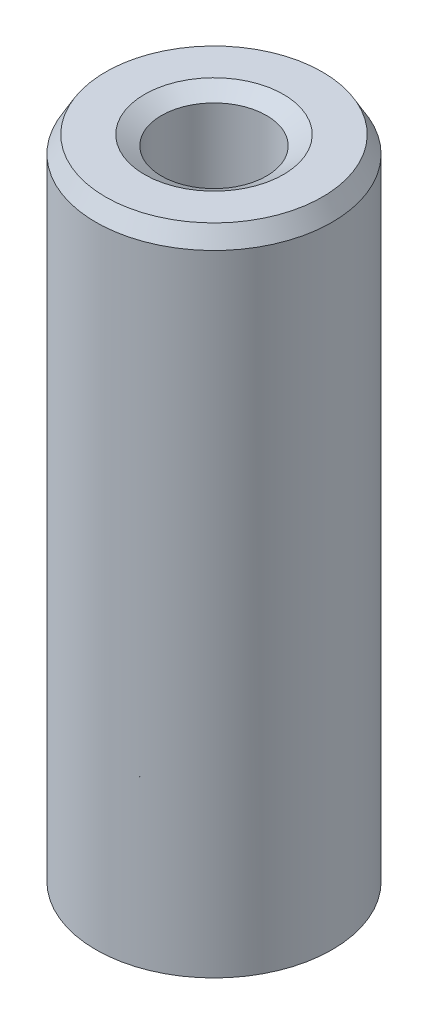
SolidWorks part; units mm, degrees
ref_plane "Front Plane" through (0, 0, 0) normal (0, 0, 1) x (1, 0, 0)
ref_plane "Top Plane" through (0, 0, 0) normal (0, 1, 0) x (1, 0, 0)
ref_plane "Right Plane" through (0, 0, 0) normal (1, 0, 0) x (0, 0, -1)
sketch "Sketch1" plane through (0, 0, 0) normal (0, 1, 0) x (1, 0, 0)
  circle A0 centre (0, 0) radius 17.5
  dimension "SLEEVE_OD" = 35
extrude "Boss-Extrude1" add sketch "Sketch1" along normal blind 97.2664
sketch "Sketch2" plane through (0, 0, 0) normal (0, 1, 0) x (1, 0, 0)
  circle A0 centre (0, 0) radius 7.7782
  dimension "BORE_D" = 15.5565
extrude "Cut-Extrude1" cut sketch "Sketch2" along normal through all
chamfer "Chamfer1" distance 2.5123 angle 30 4 edges at (0, 97.2664, 7.7782) (0, 0, 7.7782) (0, 0, 17.5) (0, 97.2664, 17.5) first distance on face at (0, 97.2664, 7.7782) first distance on face at (0, 0, 7.7782) first distance on face at (0, 97.2664, 17.5)
